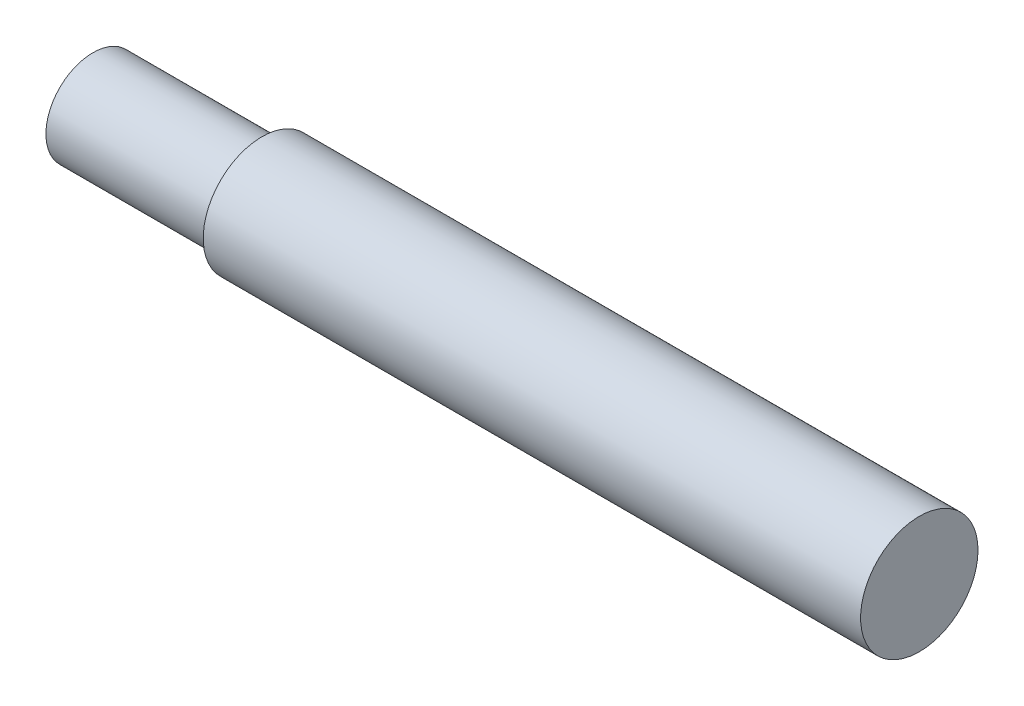
SolidWorks part; units mm, degrees
ref_plane "Front Plane" through (0, 0, 0) normal (0, 0, 1) x (1, 0, 0)
ref_plane "Top Plane" through (0, 0, 0) normal (0, 1, 0) x (1, 0, 0)
ref_plane "Right Plane" through (0, 0, 0) normal (1, 0, 0) x (0, 0, -1)
sketch "Sketch2" plane through (0, 0, 0) normal (1, 0, 0) x (0, 0, -1)
  circle A0 centre (0, 0) radius 3.9688
  dimension "D1" = 7.9375
extrude "Boss-Extrude1" add sketch "Sketch2" along normal blind 44.45
sketch "Sketch3" plane through (0, 0, 0) normal (1, 0, 0) x (0, 0, -1)
  circle A0 centre (0, 0) radius 3.175
  dimension "D1" = 6.35
extrude "Boss-Extrude2" add sketch "Sketch3" against normal blind 11.43
